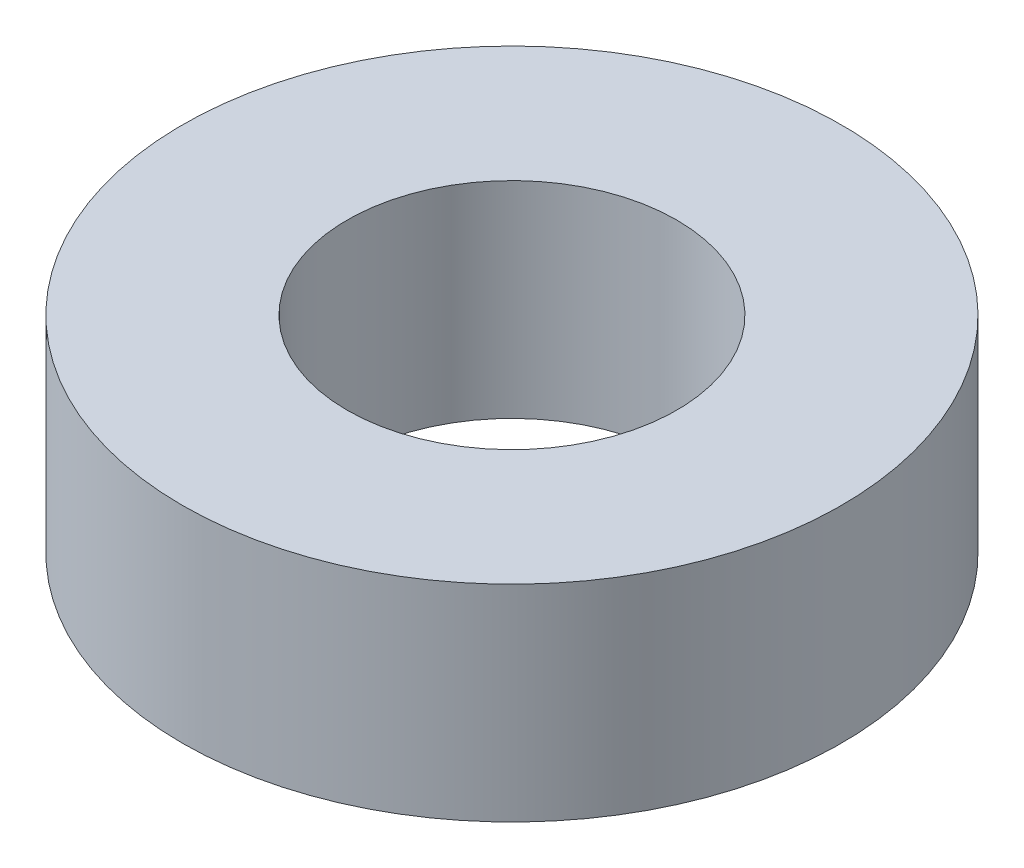
SolidWorks part; units mm, degrees
material "Chrome Stainless Steel"
ref_plane "Front Plane" through (0, 0, 0) normal (0, 0, 1) x (1, 0, 0)
ref_plane "Top Plane" through (0, 0, 0) normal (0, 1, 0) x (1, 0, 0)
ref_plane "Right Plane" through (0, 0, 0) normal (1, 0, 0) x (0, 0, -1)
sketch "Sketch1" plane through (0, 0, 0) normal (0, 1, 0) x (1, 0, 0)
  circle A0 centre (0, 0) radius 2
  circle A1 centre (0, 0) radius 4
  dimension "D1" = 8
  dimension "D2" = 4
extrude "Boss-Extrude1" add sketch "Sketch1" along normal blind 2.5
